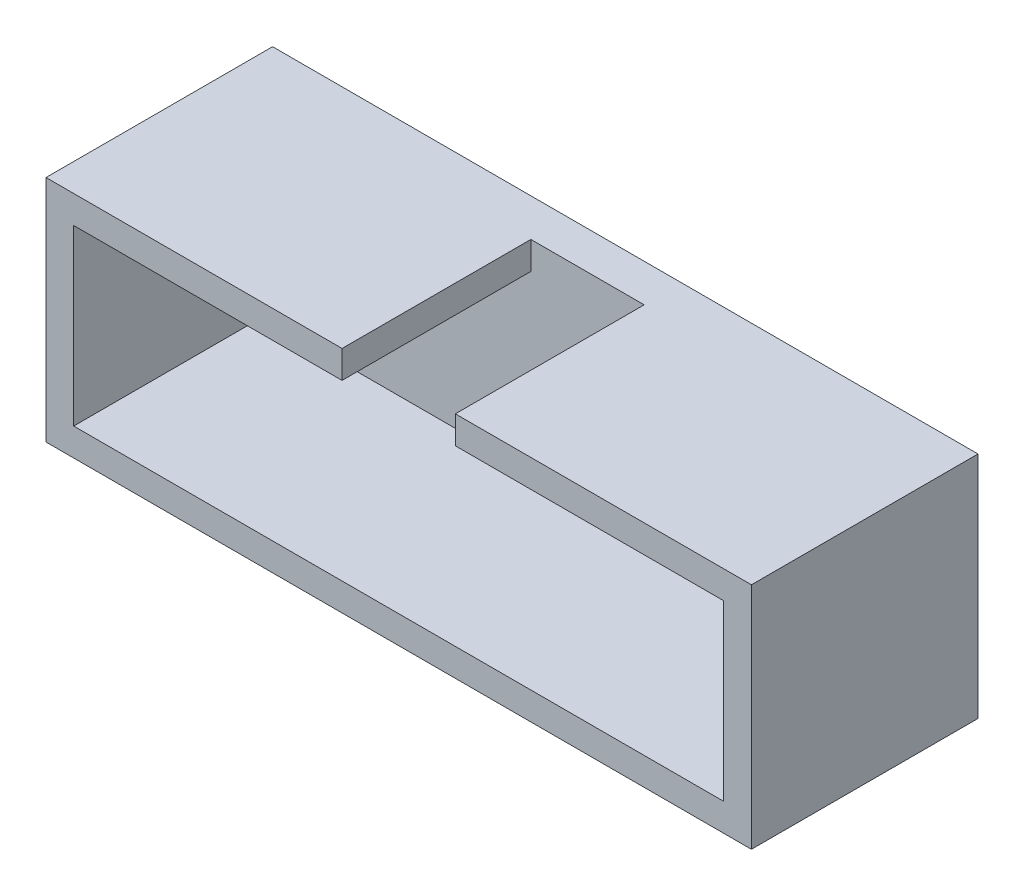
SolidWorks part; units mm, degrees
ref_plane "Спереди" through (0, 0, 0) normal (0, 0, 1) x (1, 0, 0)
ref_plane "Сверху" through (0, 0, 0) normal (0, 1, 0) x (1, 0, 0)
ref_plane "Справа" through (0, 0, 0) normal (1, 0, 0) x (0, 0, -1)
sketch "Эскиз2" plane through (0, 0, 0) normal (0, 0, 1) x (1, 0, 0)
  line L1 (-14.01, -4.55) -> (14.01, -4.55)
  line L2 (-14.01, -4.55) -> (-14.01, 4.55)
  line L3 (-14.01, 4.55) -> (14.01, 4.55)
  line L4 (14.01, -4.55) -> (14.01, 4.55)
  line L5 (-14.01, -4.55) -> (14.01, 4.55) construction
  line L6 (-14.01, 4.55) -> (14.01, -4.55) construction
  line L7 (-14.01, -4.55) -> (14.01, -4.55) construction
  point P0 (0, 0)
  dimension "D1" = 9.1
extrude "Бобышка-Вытянуть1" add sketch "Эскиз2" along normal blind 9
sketch "Эскиз3" plane through (0, 0, 9) normal (0, 0, 1) x (1, 0, 0)
  line L0 (14.01, -4.55) -> (14.01, 4.55) construction
  line L1 (12.91, -3.45) -> (-12.91, -3.45)
  line L2 (12.91, -3.45) -> (12.91, 3.45)
  line L3 (12.91, 3.45) -> (-12.91, 3.45)
  line L4 (-12.91, -3.45) -> (-12.91, 3.45)
  line L5 (12.91, -3.45) -> (-12.91, 3.45) construction
  line L6 (12.91, 3.45) -> (-12.91, -3.45) construction
  line L8 (-14.01, -4.55) -> (14.01, -4.55) construction
  point P0 (0, 0)
  dimension "D1" = 1.1
  dimension "D2" = 1.1
extrude "Вырез-Вытянуть1" cut sketch "Эскиз3" against normal blind 7.5
sketch "Эскиз4" plane through (0, 0, 9) normal (0, 0, 1) x (1, 0, 0)
  line L0 (14.01, 4.55) -> (-14.01, 4.55) construction
  line L1 (2.25, 4.55) -> (-2.25, 4.55)
  line L2 (2.25, 4.55) -> (2.25, 3.45)
  line L3 (2.25, 3.45) -> (-2.25, 3.45)
  line L4 (-2.25, 4.55) -> (-2.25, 3.45)
  line L5 (12.91, 3.45) -> (-12.91, 3.45) construction
  point P8 (0, 4.55)
  dimension "D1" = 4.5
extrude "Вырез-Вытянуть2" cut sketch "Эскиз4" against normal blind 7.5
